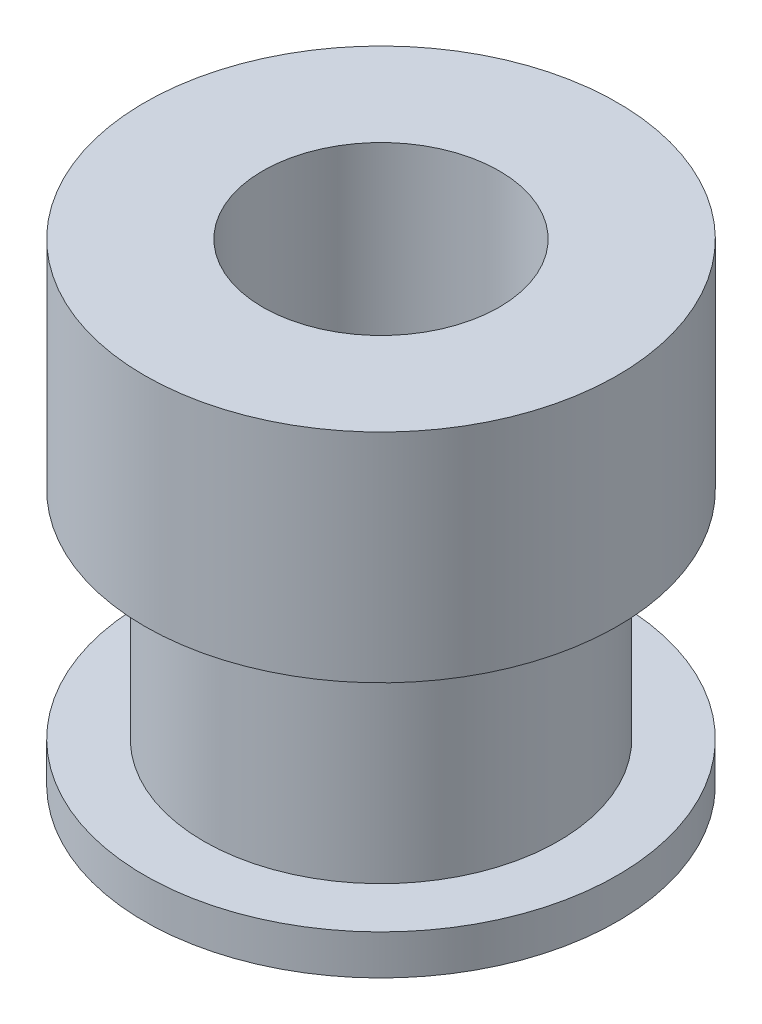
SolidWorks part; units mm, degrees
ref_plane "前视基准面" through (0, 0, 0) normal (0, 0, 1) x (1, 0, 0)
ref_plane "上视基准面" through (0, 0, 0) normal (0, 1, 0) x (1, 0, 0)
ref_plane "右视基准面" through (0, 0, 0) normal (1, 0, 0) x (0, 0, -1)
other "Configuration Table"
sketch "草图1" plane through (0, 0, 0) normal (0, 1, 0) x (1, 0, 0)
  circle A0 centre (0, 0) radius 8
  dimension "D1" = 16
extrude "凸台-拉伸1" add sketch "草图1" along normal blind 1.35 contours A0 region at (0, 0, 0)
sketch "草图4" plane through (0, 1.35, 0) normal (0, 1, 0) x (1, 0, 0)
  circle A0 centre (0, 0) radius 6
  dimension "D1" = 12
extrude "凸台-拉伸3" add sketch "草图4" along normal blind 7.3
extrude "凸台-拉伸4" add sketch "草图1<3>" along normal blind 7.35 from surface starting at face at (0, 8.65, 6)
sketch "草图1<3>" plane through (0, 0, 0) normal (0, 1, 0) x (1, 0, 0) same geometry as "草图1"
sketch "草图5" plane through (0, 0, 0) normal (0, -1, 0) x (1, 0, 0)
  circle A0 centre (0, 0) radius 4
  dimension "D1" = 8
extrude "切除-拉伸1" cut sketch "草图5" against normal through all
